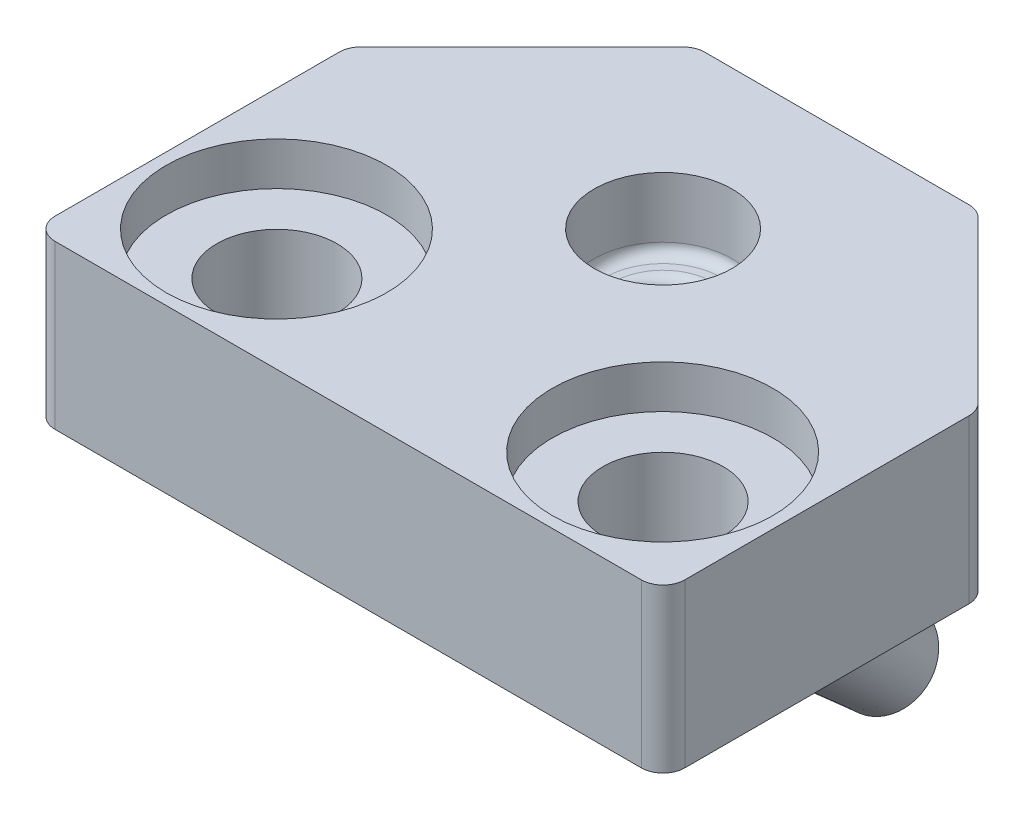
SolidWorks part; units mm, degrees
ref_plane "Front Plane" through (0, 0, 0) normal (0, 0, 1) x (1, 0, 0)
ref_plane "Top Plane" through (0, 0, 0) normal (0, 1, 0) x (1, 0, 0)
ref_plane "Right Plane" through (0, 0, 0) normal (1, 0, 0) x (0, 0, -1)
sketch "Sketch11" plane through (0, 0, 0) normal (0, 1, 0) x (1, 0, 0)
  line L0 (-14.5, 0) -> (-14.5, -14.5)
  line L7 (14.5, 0) -> (6.5, 8)
  line L8 (6.5, 8) -> (-6.5, 8)
  line L9 (-6.5, 8) -> (-14.5, 0)
  line L11 (-14.5, -14.5) -> (14.5, -14.5)
  line L13 (0, 0) -> (0, -14.5) construction
  line L15 (14.5, 0) -> (14.5, -14.5)
  circle A0 centre (-8.89, -8.89) radius 2.77
  circle A1 centre (8.89, -8.89) radius 2.77
  circle A2 centre (-8.89, -8.89) radius 5.08 construction
  circle A3 centre (8.89, -8.89) radius 5.08 construction
  point P14 (0, 0)
  point P15 (5.8357, 8)
  dimension "D1" = 8
  dimension "D3" = 5.54
  dimension "D7" = 10.16
  dimension "D2" = 14.5
  dimension "D4" = 8.89
  dimension "D5" = 8.89
  dimension "D6" = 14.5
  dimension "D8" = 135
extrude "MainHolder" add sketch "Sketch11" along normal blind 7.5
sketch "Sketch12" plane through (0, 7.5, 0) normal (0, 1, 0) x (1, 0, 0)
  circle A0 centre (0, 0) radius 3.175
  dimension "D1" = 6.35
extrude "MagnetCutout" cut sketch "Sketch12" against normal blind 3.28
sketch "Sketch13" plane through (0, 4.22, 0) normal (0, 1, 0) x (1, 0, 0)
  circle A0 centre (0, 0) radius 1.8
  dimension "D1" = 3.6
extrude "MagnetHole" cut sketch "Sketch13" against normal up to next
sketch "DrainPath" plane through (0, 0, 0) normal (1, 0, 0) x (0, 0, -1)
  line L0 (0, 0) -> (0, -2)
  line L1 (1.7574, -6.2426) -> (10.2426, -14.7279)
  arc A0 (1.7574, -6.2426) -> (0, -2) centre (6, -2) cw
  point P7 (0, -4.4853)
  dimension "D3" = 6
  dimension "D1" = 135
  dimension "D2" = 12
  dimension "D4" = 2
sketch "Sketch14" plane through (0, 7.5, 0) normal (0, 1, 0) x (1, 0, 0)
  line L0 (0, 0) -> (0, -14.5) construction
  line L1 (-14.5, -14.5) -> (14.5, -14.5) construction
  circle A0 centre (-8.8896, -8.9111) radius 5.08
  circle A1 centre (8.8896, -8.9111) radius 5.08
  dimension "D1" = 10.16
extrude "Cut-Extrude1" cut sketch "Sketch14" against normal blind 1.98
sketch "DrainOpening" plane through (0, 0, 0) normal (0, -1, 0) x (1, 0, 0)
  circle A0 centre (0, 0) radius 1.125
  circle A2 centre (0, 0) radius 2
  dimension "D1" = 2.25
  dimension "D2" = 4
sweep "Drain" add profiles "DrainOpening" path "DrainPath"
ref_axis "DrainOutAxis" through (0, -5.4471, -0.9619) along (0, -0.7071, -0.7071)
ref_plane "DrainMidPlain" through (0, 0, 0) normal (-1, 0, 0) x (0, -0.7071, -0.7071)
sketch "BarbOutline" plane through (0, 0, 0) normal (-1, 0, 0) x (0, -0.7071, -0.7071)
  line L0 (17.6569, 1.1716) -> (11.6569, 1.1716)
  line L1 (11.6569, 1.1716) -> (11.6569, 0.7966)
  line L2 (11.6569, 0.7966) -> (17.6569, 1.1716)
  line L3 (5.6569, 1.1716) -> (17.6569, 1.1716) construction
  line L4 (4.5319, 3.1716) -> (18.7819, 3.1716) construction
  line L8 (5.6569, 1.1716) -> (17.6569, 1.1716) construction
  dimension "D1" = 6
  dimension "D2" = 2.375
revolve "Barb" add sketch "BarbOutline" angle 360 about axis through (0, -5.4471, -0.9619) along (0, -0.7071, -0.7071)
ref_axis "MagnetAxis" through (0, 0, 0) along (0, 1, 0)
fillet "Fillet1" radius 0.5 3 edges at (0, 0, -1.8) (0, 4.22, 1.8) (0, 4.22, 3.175)
fillet "DrainBottomFillet" radius 2 1 edges at (0, 0, -2) type face fillet first side face at (0, 0, -2) second side face at (0, -2, -2)
fillet "BarbFillet" radius 1 1 edges at (0, -11.8995, -4.5858)
sketch "Sketch15" plane through (0, 7.5, 0) normal (0, 1, 0) x (1, 0, 0)
  circle A0 centre (0, 0) radius 3.175
  dimension "D1" = 6.35
fillet "Fillet2" radius 1 6 edges at (6.5, 3.75, -8) (14.5, 3.75, 0) (14.5, 3.75, 14.5) (-14.5, 3.75, 14.5) (-14.5, 3.75, 0) (-6.5, 3.75, -8)
equation "\"channel_diameter\"= 4mm"
equation "\"channel_length\"= 12mm"
equation "\"barb_length\"= 6mm"
equation "\"lumen_diameter\"= 2.25mm"
equation "\"magnet_holder_thickness\"= 7.5"
equation "\"magnet_diameter\"=25.4"
equation "\"magnet_holder_tolerance\"= 0.1mm"
equation "\"magnet_thickness\"= 3.18mm"
equation "\"D1@MainHolder\" = \"magnet_holder_thickness\""
equation "\"D1@MagnetCutout\" = \"magnet_thickness\" + \"magnet_holder_tolerance\""
equation "\"magnet_hole_small\"= 4.83mm"
equation "\"D1@Sketch13\"=\"channel_diameter\" * 0.9"
equation "\"drain_angle\"= 135"
equation "\"D1@DrainPath\" = \"drain_angle\""
equation "\"D2@DrainPath\" = \"barb_length\" * 2"
equation "\"D1@DrainOpening\" = \"lumen_diameter\""
equation "\"D1@BarbOutline\" = \"barb_length\""
equation "\"D2@BarbOutline\"=\"channel_diameter\" / 2 + \"barb_extension\""
equation "\"FilletBase\"=3"
equation "\"barb_extension\"= 0.75mm / 2"
equation "\"D2@DrainOpening\"=\"channel_diameter\""
